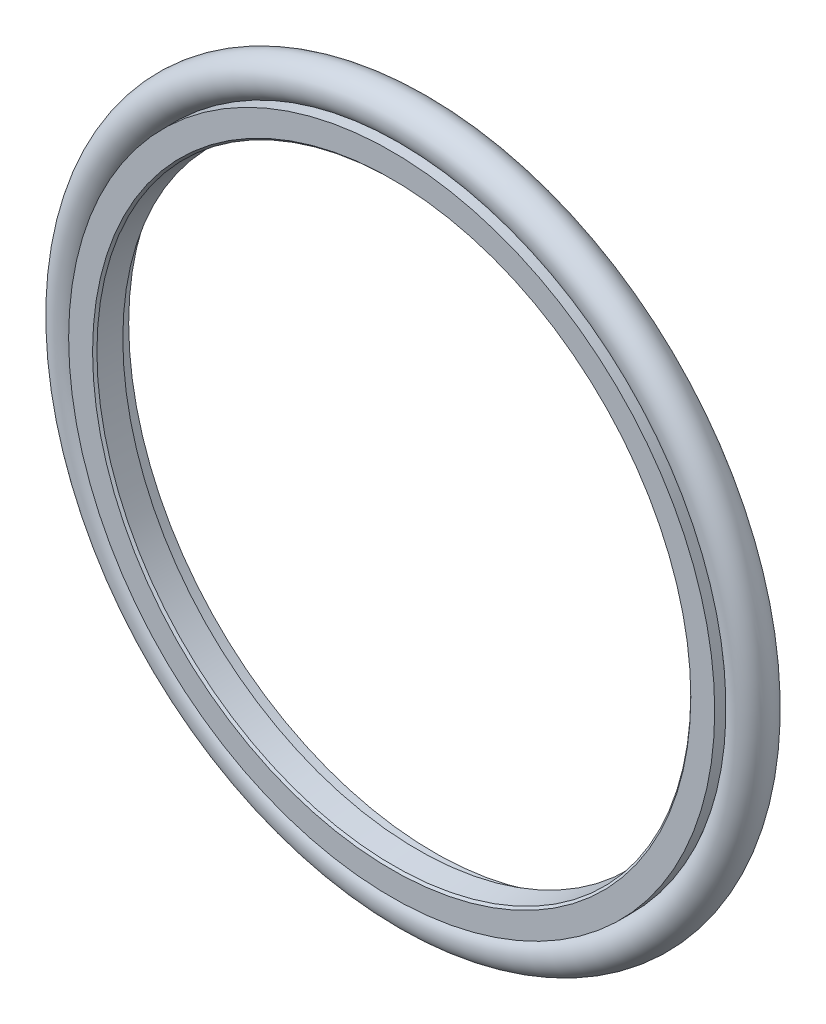
SolidWorks part; units mm, degrees
material "PTFE+NBR"
ref_plane "Front Plane" through (0, 0, 0) normal (0, 0, 1) x (1, 0, 0)
ref_plane "Top Plane" through (0, 0, 0) normal (0, 1, 0) x (1, 0, 0)
ref_plane "Right Plane" through (0, 0, 0) normal (1, 0, 0) x (0, 0, -1)
sketch "Sketch1" plane through (0, 0, 0) normal (1, 0, 0) x (0, 0, -1)
  line L0 (0, 28.1) -> (0, 29.7)
  line L1 (-3.92, 29.7) -> (0, 29.7)
  line L2 (-3.92, 29.7) -> (-3.92, 27.5)
  line L3 (-1.96, 29.7) -> (-1.96, 56.7993) construction
  line L4 (-1.5, 27.14) -> (-3.72, 27.3)
  line L5 (-1.5, 27.14) -> (-0.9, 28.1)
  line L6 (0, 0) -> (-16.4728, 0) construction
  line L7 (0, 28.1) -> (-0.9, 28.1)
  line L9 (-3.92, 29.7) -> (0, 29.7) construction
  line L10 (-3.72, 27.3) -> (-3.92, 27.5)
  point P13 (-0.9, 22.2)
  dimension "D2" = 2.2
  dimension "D4" = 2.4
  dimension "D10" = 1.5
  dimension "D1" = 3.92
  dimension "D3" = 59.4
  dimension "D5" = 2.56
  dimension "D6" = 1.6
  dimension "D7" = 0.9
  dimension "D8" = 0.2
  dimension "D9" = 54.28
  dimension "D11" = 56.2
  dimension "D12" = 55
revolve "Revolve1" add sketch "Sketch1" angle 360 about L6
sketch "Sketch4" plane through (0, 0, 0) normal (1, 0, 0) x (0, 0, -1)
  line L0 (0, 0) -> (-3.92, 0) construction
  line L2 (-1.96, 0) -> (-1.96, 52.8756) construction
  line L3 (-3.92, 29.7) -> (-3.92, -29.7) construction
  circle A0 centre (-1.96, 31.265) radius 1.765
  dimension "D1" = 59
  dimension "D2" = 3.53
revolve "Revolve2" add sketch "Sketch4" angle 360 about L0
ref_axis "Axis1" through (0, 0, 0) along (0, 0, 1)
